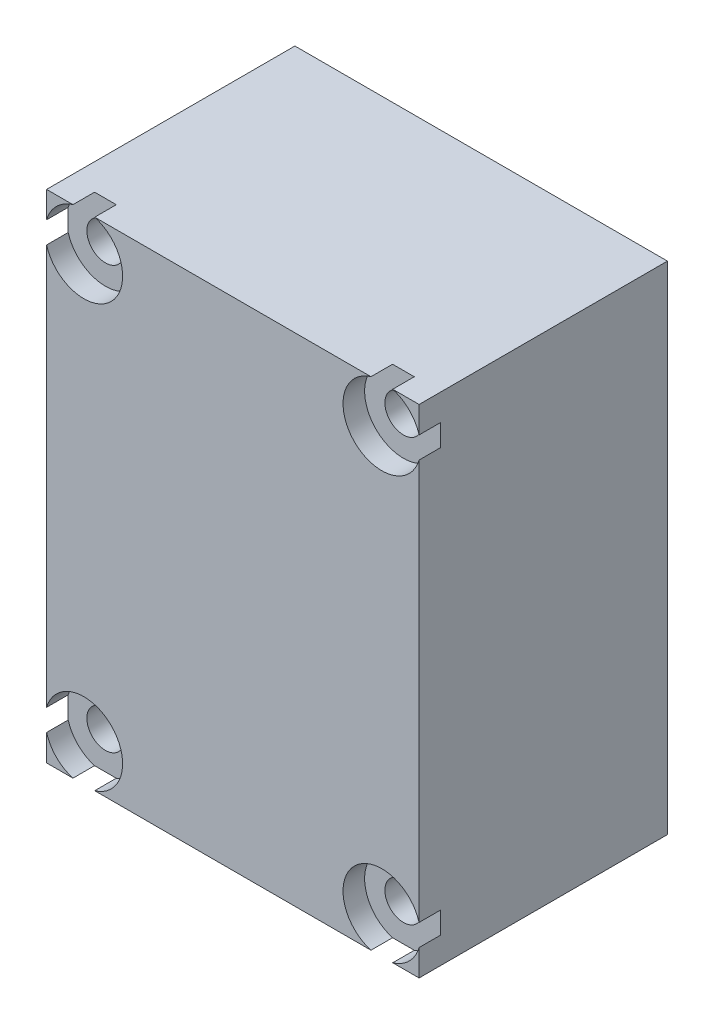
SolidWorks part; units mm, degrees
ref_plane "Front Plane" through (0, 0, 0) normal (0, 0, 1) x (1, 0, 0)
ref_plane "Top Plane" through (0, 0, 0) normal (0, 1, 0) x (1, 0, 0)
ref_plane "Right Plane" through (0, 0, 0) normal (1, 0, 0) x (0, 0, -1)
sketch "Sketch2" plane through (0, 0, 0) normal (0, 0, 1) x (1, 0, 0)
  line L1 (-51.5651, 39.2476) -> (-13.4651, 39.2476)
  line L2 (-51.5651, 39.2476) -> (-51.5651, -11.5524)
  line L3 (-51.5651, -11.5524) -> (-13.4651, -11.5524)
  line L4 (-13.4651, 39.2476) -> (-13.4651, -11.5524)
  dimension "D1" = 50.8
  dimension "D2" = 38.1
extrude "Boss-Extrude1" add sketch "Sketch2" along normal blind 25.4
hole_wizard "CBORE for #6 Binding Head Machine Screw1" positions "3DSketch1" profile "Sketch3" counterbore size "#6" standard "ANSI Inch" end condition through all
sketch3d "3DSketch1"
  line L0 (-13.4651, 39.2476, 25.4) -> (-51.5651, 39.2476, 25.4) construction
  line L1 (-51.5651, 39.2476, 25.4) -> (-51.5651, -11.5524, 25.4) construction
  line L2 (-13.4651, -11.5524, 25.4) -> (-13.4651, 39.2476, 25.4) construction
  line L3 (-51.5651, -11.5524, 25.4) -> (-13.4651, -11.5524, 25.4) construction
  point P0 (-47.7551, 35.4376, 25.4)
  point P2 (-17.2751, 35.4376, 25.4)
  point P4 (-47.7551, -7.7424, 25.4)
  point P6 (-17.2751, -7.7424, 25.4)
  dimension "D1" = 3.81
  dimension "D2" = 3.81
  dimension "D3" = 3.81
  dimension "D4" = 3.81
  dimension "D5" = 3.81
  dimension "D6" = 3.81
  dimension "D7" = 3.81
  dimension "D8" = 3.81
sketch "Sketch3" plane through (-47.7551, 35.4376, 25.4) normal (1, 0, 0) x (0, -1, 0)
  line L0 (0, 0) -> (0, 25.4)
  line L1 (0, 25.4) -> (1.8986, 25.4)
  line L3 (1.8986, 25.4) -> (1.8987, 2.2098)
  line L4 (1.8987, 2.2098) -> (3.9688, 2.2098)
  line L5 (3.9688, 2.2098) -> (3.9687, 0)
  line L7 (3.9687, 0) -> (0, 0)
  line L11 (0, -6.35) -> (0, 107.95) construction
  dimension "Thru Hole Dia." = 3.7973
  dimension "Thru Hole Depth" = 25.4
  dimension "C'Bore Dia." = 7.9375
  dimension "C'Bore Depth" = 2.2098
